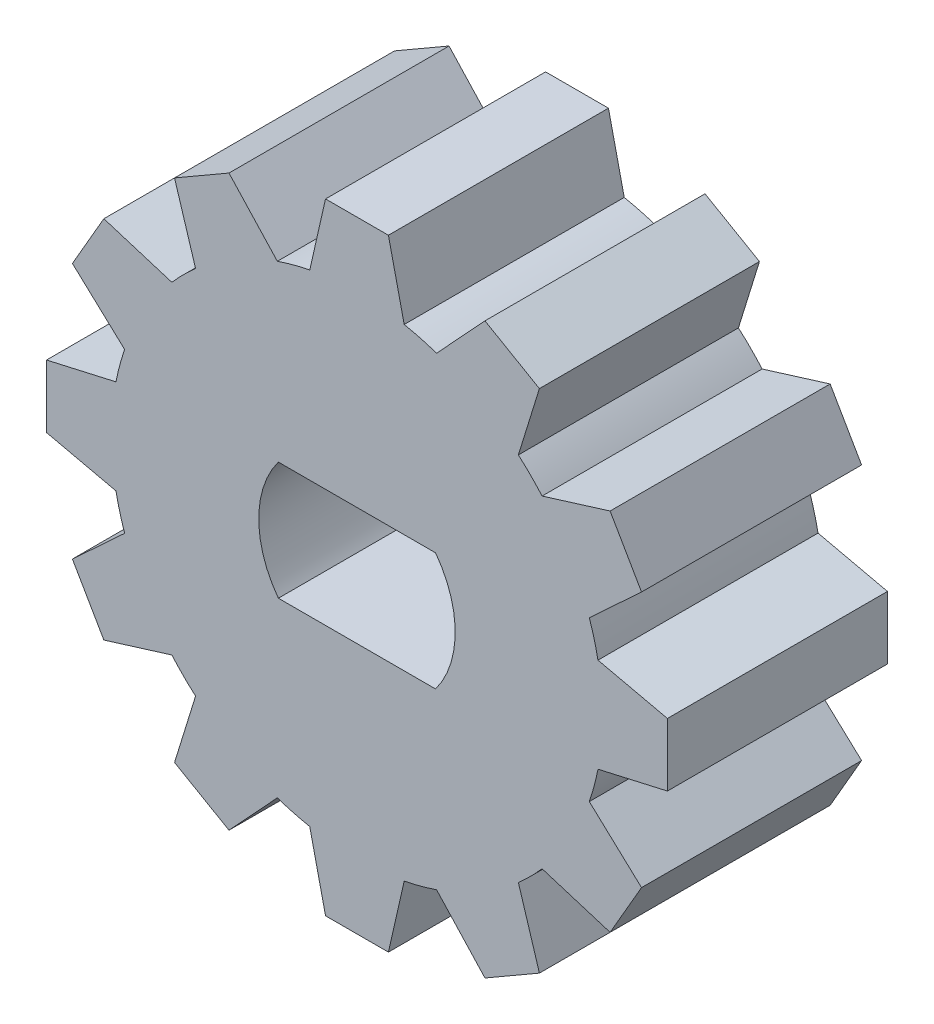
SolidWorks part; units mm, degrees
ref_plane "Front Plane" through (0, 0, 0) normal (0, 0, 1) x (1, 0, 0)
ref_plane "Top Plane" through (0, 0, 0) normal (0, 1, 0) x (1, 0, 0)
ref_plane "Right Plane" through (0, 0, 0) normal (1, 0, 0) x (0, 0, -1)
sketch "Sketch1" plane through (0, 0, 0) normal (0, 0, 1) x (1, 0, 0)
  circle A0 centre (0, 0) radius 6.25
  dimension "D1" = 12.5
extrude "Boss-Extrude1" add sketch "Sketch1" along normal blind 5.6
sketch "Sketch3" plane through (0, 0, 0) normal (0, 0, 1) x (1, 0, 0)
  line L0 (0, -7.9) -> (0, 7.9) construction
  line L1 (-0.8, 7.9) -> (0.8, 7.9)
  line L2 (-0.8, 7.9) -> (-1.3, 5.7)
  line L3 (-1.3, 5.7) -> (1.3, 5.7)
  line L4 (1.3, 5.7) -> (0.8, 7.9)
  point P3 (0, 0)
  point P4 (0, 5.7)
  point P6 (0, 7.9)
  dimension "D1" = 7.9
  dimension "D2" = 2.6
  dimension "D3" = 1.6
  dimension "D4" = 5.7
extrude "Boss-Extrude2" add sketch "Sketch3" along normal blind 5.6
ref_axis "Axis2" through (0, 0, 5.6) along (0, 0, -1)
pattern_circular "CirPattern1" count 12 every 30 about axis through (0, 0, 0) along (0, 0, 1) of "Boss-Extrude2"
sketch "Sketch4" plane through (0, 0, 0) normal (0, 0, 1) x (1, 0, 0)
  line L1 (-2, -1.5) -> (2, -1.5)
  line L2 (-2, 1.5) -> (2, 1.5)
  arc A1 (2, -1.5) -> (2, 1.5) centre (0, 0) ccw
  circle A2 centre (0, 0) radius 1.5 construction
  arc A3 (-2, 1.5) -> (-2, -1.5) centre (0, 0) ccw
  point P5 (0, -1.5)
  point P8 (0, 1.5)
  dimension "D1" = 4
  dimension "D2" = 2.5
extrude "Cut-Extrude1" cut sketch "Sketch4" along normal blind 7
